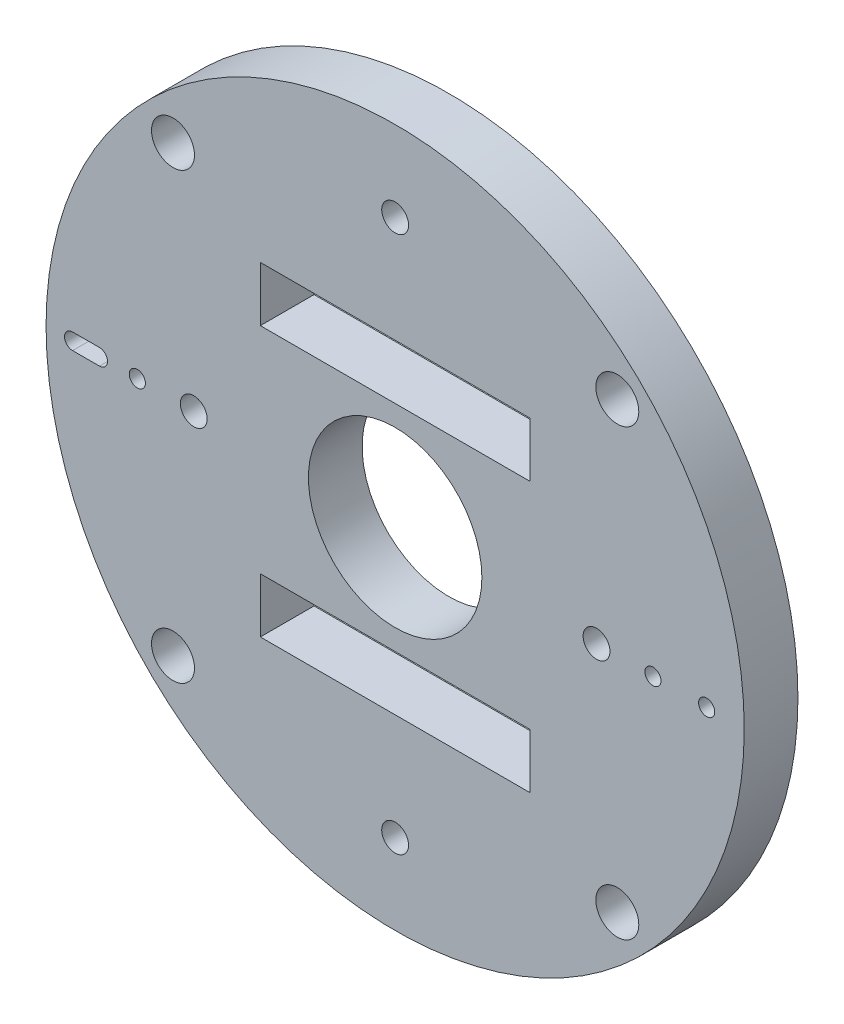
SolidWorks part; units mm, degrees
ref_plane "Front Plane" through (0, 0, 0) normal (0, 0, 1) x (1, 0, 0)
ref_plane "Top Plane" through (0, 0, 0) normal (0, 1, 0) x (1, 0, 0)
ref_plane "Right Plane" through (0, 0, 0) normal (1, 0, 0) x (0, 0, -1)
sketch "Sketch1" plane through (0, 0, 0) normal (0, 0, 1) x (1, 0, 0)
  line L31 (-25.1, -20) -> (25.1, -20)
  line L32 (-55.0566, 0) -> (-60.0566, 0) construction
  line L35 (-55.0566, -1.5) -> (-60.0566, -1.5)
  line L36 (-55.0566, 1.5) -> (-60.0566, 1.5)
  line L37 (25.1, -20) -> (25.1, -30.2)
  line L38 (25.1, -30.2) -> (-25.1, -30.2)
  line L39 (-25.1, -30.2) -> (-25.1, -20)
  line L40 (-25.1, 30.2) -> (25.1, 30.2)
  line L41 (-25.1, 30.2) -> (-25.1, 20)
  line L42 (-25.1, 20) -> (25.1, 20)
  line L43 (25.1, 20) -> (25.1, 30.2)
  circle A0 centre (0, 0) radius 65
  circle A1 centre (-37.5, 0) radius 2.5
  circle A2 centre (37.5, 0) radius 2.5
  circle A3 centre (0, 50) radius 2.5
  circle A4 centre (0, -50) radius 2.5
  circle A6 centre (0, 0) radius 16.15
  circle A12 centre (-41.3657, 41.3657) radius 4
  circle A13 centre (41.3657, -41.3657) radius 4
  circle A14 centre (41.3657, 41.3657) radius 4
  circle A15 centre (-41.3657, -41.3657) radius 4
  arc A25 (-55.0566, -1.5) -> (-55.0566, 1.5) centre (-55.0566, 0) ccw
  arc A26 (-60.0566, 1.5) -> (-60.0566, -1.5) centre (-60.0566, 0) ccw
  circle A27 centre (48, 0) radius 1.5
  circle A28 centre (58, 0) radius 1.5
  circle A29 centre (-48, 0) radius 1.5
  point P6 (0, 0)
  point P11 (0, 0)
  point P23 (29.6754, -19.9128)
  point P24 (0, -20)
  point P26 (0, 0)
  point P37 (0, 0)
  point P44 (-57.5566, 0)
extrude "Boss-Extrude1" add sketch "Sketch1" along normal blind 10
